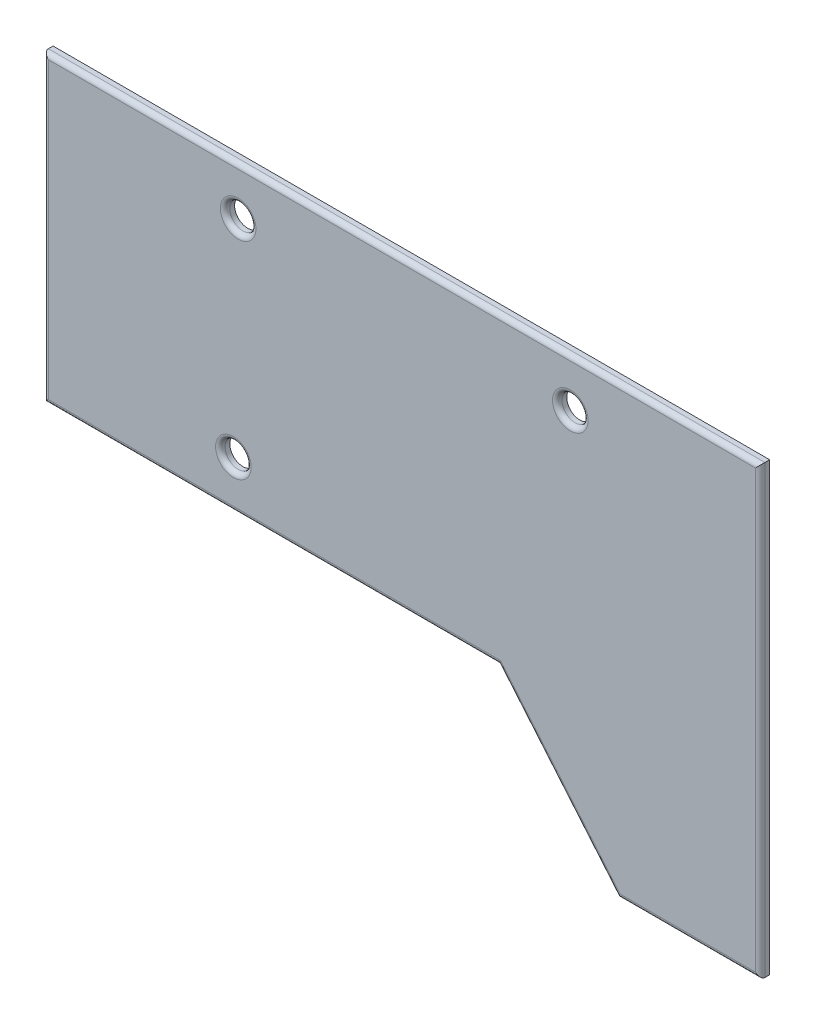
SolidWorks part; units mm, degrees
ref_plane "Front Plane" through (0, 0, 0) normal (0, 0, 1) x (1, 0, 0)
ref_plane "Top Plane" through (0, 0, 0) normal (0, 1, 0) x (1, 0, 0)
ref_plane "Right Plane" through (0, 0, 0) normal (1, 0, 0) x (0, 0, -1)
sketch "Sketch1" plane through (0, 0, 0) normal (0, 0, 1) x (1, 0, 0)
  line L0 (0, 0) -> (0, 64)
  line L1 (0, 64) -> (151, 64)
  line L2 (151, 64) -> (151, -30)
  line L3 (151, -30) -> (121, -30)
  line L4 (121, -30) -> (95.827, 0)
  line L5 (95.827, 0) -> (0, 0)
  circle A0 centre (41, 54) radius 2.75
  circle A1 centre (111, 54) radius 2.75
  circle A2 centre (40, 10) radius 2.75
  point P13 (0, 0)
  dimension "D11" = 5.5
  dimension "D1" = 30
  dimension "D2" = 151
  dimension "D3" = 130
  dimension "D4" = 30
  dimension "D5" = 64
  dimension "D6" = 10
  dimension "D7" = 10
  dimension "D8" = 70
  dimension "D9" = 40
  dimension "D10" = 40
extrude "Boss-Extrude1" add sketch "Sketch1" along normal blind 2
fillet "Fillet1" radius 1 9 edges at (42.75, 10, 2) (113.75, 54, 2) (43.75, 54, 2) (0, 32, 2) (75.5, 64, 2) (151, 17, 2) (136, -30, 2) (108.4135, -15, 2) (47.9135, 0, 2)
